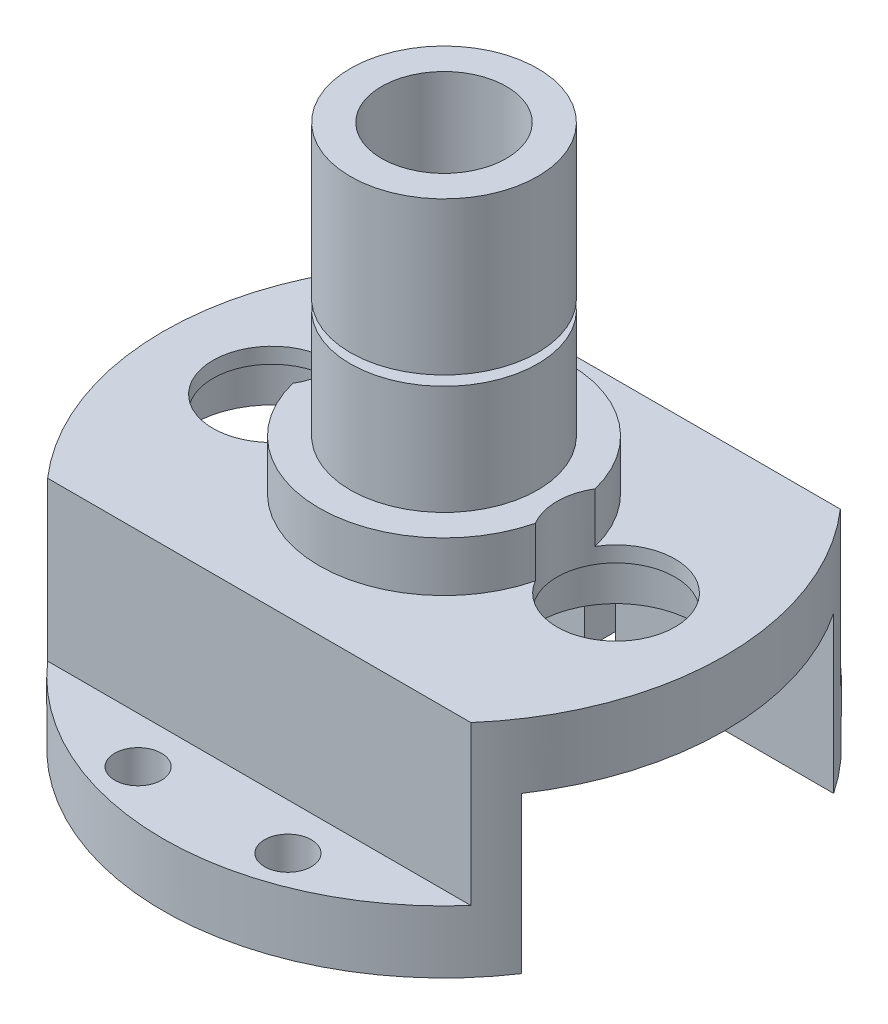
SolidWorks part; units mm, degrees
ref_plane "Front Plane" through (0, 0, 0) normal (0, 0, 1) x (1, 0, 0)
ref_plane "Top Plane" through (0, 0, 0) normal (0, 1, 0) x (1, 0, 0)
ref_plane "Right Plane" through (0, 0, 0) normal (1, 0, 0) x (0, 0, -1)
sketch "Sketch1" plane through (0, 0, 0) normal (0, 1, 0) x (1, 0, 0)
  circle A0 centre (0, 0) radius 12.7
  circle A1 centre (0, 0) radius 6.35
  dimension "D1" = 25.4
  dimension "D2" = 12.7
extrude "Boss-Extrude1" add sketch "Sketch1" along normal blind 5.08
sketch "Sketch2" plane through (0, 5.08, 0) normal (0, 1, 0) x (1, 0, 0)
  circle A0 centre (0, 0) radius 6.35
  circle A1 centre (0, 0) radius 9.525
  dimension "D1" = 19.05
  dimension "D2" = 3.175
extrude "Boss-Extrude2" add sketch "Sketch2" along normal blind 27.6225
ref_plane "Plane1" through (0, 16.1925, 0) normal (0, 1, 0) x (-1, 0, 0)
sketch "Sketch3" plane through (0, 16.1925, 0) normal (0, 1, 0) x (-1, 0, 0)
  circle A0 centre (0, 0) radius 7.4676
  dimension "D1" = 14.9352
extrude "Cut-Extrude1" cut sketch "Sketch3" along normal blind 0.9906 flip side to cut
sketch "Sketch4" plane through (0, 0, 0) normal (0, -1, 0) x (1, 0, 0)
  circle A0 centre (0, 0) radius 12.7 construction
  circle A4 centre (0, 0) radius 12.7
  circle A5 centre (0, 0) radius 15.875
  dimension "D4" = 31.75
sketch "Sketch5" plane through (0, 0, 0) normal (0, -1, 0) x (1, 0, 0)
  line L0 (-17.5, 0) -> (17.5, 0) construction
  circle A0 centre (0, 0) radius 7.9375
  circle A1 centre (0, 0) radius 17.5 construction
  circle A2 centre (17.5, 0) radius 6
  circle A3 centre (-17.5, 0) radius 6
  circle A4 centre (0, 0) radius 28.575
  dimension "D1" = 15.875
  dimension "D2" = 35
  dimension "D3" = 12
  dimension "D4" = 57.15
extrude "Boss-Extrude4" add sketch "Sketch5" along normal blind 6.5875
sketch "Sketch6" plane through (0, -6.5875, 0) normal (0, -1, 0) x (1, 0, 0)
  circle A0 centre (-17.5, 0) radius 8
  circle A1 centre (17.5, 0) radius 8
  dimension "D1" = 16
extrude "Cut-Extrude5" cut sketch "Sketch6" against normal blind 5
sketch "Sketch8" plane through (0, -6.5875, 0) normal (0, -1, 0) x (1, 0, 0)
  line L0 (-23.7595, -15.875) -> (23.7595, -15.875)
  line L1 (-23.7595, 15.875) -> (23.7595, 15.875)
  line L2 (-23.7595, -15.875) -> (-23.7595, 15.875) construction
  line L3 (23.7595, -15.875) -> (23.7595, 15.875) construction
  circle A0 centre (0, 0) radius 28.575 construction
  circle M3 centre (0, 0) radius 28.575
  dimension "D1" = 31.75
extrude "Boss-Extrude5" add sketch "Sketch8" along normal blind 15.875 contours L0 M3 | L1 M3 region at (0, -6.5875, -21.0662) region at (0, -6.5875, 21.0662)
sketch "Sketch9" plane through (0, -22.4625, 0) normal (0, -1, 0) x (1, 0, 0)
  line L0 (7.62, 23.495) -> (-7.62, 23.495) construction
  line L1 (17.5, 0) -> (0, 0) construction
  circle A0 centre (7.62, 23.495) radius 2.3813
  circle A1 centre (-7.62, 23.495) radius 2.3813
  circle A2 centre (-7.62, -23.495) radius 2.3813
  circle A3 centre (7.62, -23.495) radius 2.3813
  dimension "D3" = 4.7625
  dimension "D1" = 7.62
  dimension "D2" = 23.495
  dimension "D4" = 7.62
extrude "Cut-Extrude7" cut sketch "Sketch9" against normal up to surface (22.4625 mm away) up to face at (0, 0, 0)
sketch "Sketch11" plane through (0, 0, -15.875) normal (0, 0, 1) x (1, 0, 0)
  line L0 (1.5875, -22.4625) -> (1.5875, -8.175)
  line L1 (-23.7595, -22.4625) -> (23.7595, -22.4625) construction
  line L2 (-23.7595, -6.5875) -> (23.7595, -6.5875) construction
  line L3 (-1.5875, -22.4625) -> (-1.5875, -8.175)
  line L4 (1.5875, -22.4625) -> (23.7595, -22.4625) construction
  line L5 (-1.5875, -22.4625) -> (-23.7595, -22.4625) construction
  line L6 (23.7595, -22.4625) -> (23.7595, -6.5875) construction
  line L7 (-23.7595, -22.4625) -> (-23.7595, -6.5875) construction
  arc A0 (1.5875, -8.175) -> (-1.5875, -8.175) centre (0, -8.175) ccw
  line M6 (-23.7595, -22.4625) -> (23.7595, -22.4625)
  dimension "D1" = 3.175
extrude "Cut-Extrude9" cut sketch "Sketch11" against normal through all contours L0 A0 L3 M6 region at (0, -14.6913, -15.875)
ref_plane "Plane2" through (0, -22.4625, 0) normal (0, -1, 0) x (-1, 0, 0)
ref_axis "Axis1" through (0, 32.7025, 0) along (0, -1, 0)
ref_axis "Axis2" through (-17.5, -1.5875, 0) along (0, -1, 0)
ref_axis "Axis3" through (17.5, -1.5875, 0) along (0, -1, 0)
sketch "Sketch12" plane through (0, 0, 0) normal (0, 1, 0) x (1, 0, 0)
  line L0 (7.62, -23.495) -> (7.62, -28.575) construction
  line L1 (28.575, -18.796) -> (-28.575, -18.796)
  line L2 (28.575, -18.796) -> (28.575, -28.575)
  line L3 (28.575, -28.575) -> (-28.575, -28.575)
  line L4 (-28.575, -18.796) -> (-28.575, -28.575)
  line L5 (0, 0) -> (-17.5, 0) construction
  line L6 (-28.575, 18.796) -> (-28.575, 28.575)
  line L7 (28.575, 18.796) -> (-28.575, 18.796)
  line L8 (28.575, 18.796) -> (28.575, 28.575)
  line L9 (28.575, 28.575) -> (-28.575, 28.575)
  circle A0 centre (0, 0) radius 28.575 construction
  dimension "D1" = 4.699
extrude "Cut-Extrude10" cut sketch "Sketch12" against normal offset from surface (16.1125 mm away) 6.35 up to face at (-7.62, -22.4625, 21.1137)
extrude "Cut-Extrude11" cut sketch "Sketch5<4>" against normal up to surface (5.08 mm away) contours A3 | A2 up to face at (0, 5.08, 12.7)
sketch "Sketch5<4>" plane through (0, 0, 0) normal (0, -1, 0) x (1, 0, 0) same geometry as "Sketch5"
sketch "Sketch13" plane through (0, 0, 0) normal (1, 0, 0) x (0, 0, -1)
  line L0 (15.875, -6.5875) -> (7.9375, 0)
  line L1 (15.875, -6.5875) -> (7.9375, -6.5875)
  line L2 (7.9375, -6.5875) -> (7.9375, 0)
  line L3 (7.9375, -6.5875) -> (6.3356, -6.5875)
  line L4 (6.3356, -6.5875) -> (6.35, 0)
  line L5 (6.35, 0) -> (6.35, 32.7025) construction
  line L6 (6.35, 0) -> (7.9375, 0)
  line L7 (7.9375, 0) -> (7.953, 0.0084)
  dimension "D1" = 0.125
extrude "Cut-Extrude12" cut sketch "Sketch13" against normal mid plane 3.175 contours L6 L4 L3 L2 | L2 L1 L0 region at (0, -4.3917, -10.5833) region at (0, -3.2987, -7.1402)
fillet "Fillet1" radius 1.5875 2 edges at (-1.5875, -3.2937, -11.9063) (1.5875, -3.2937, -11.9063)
